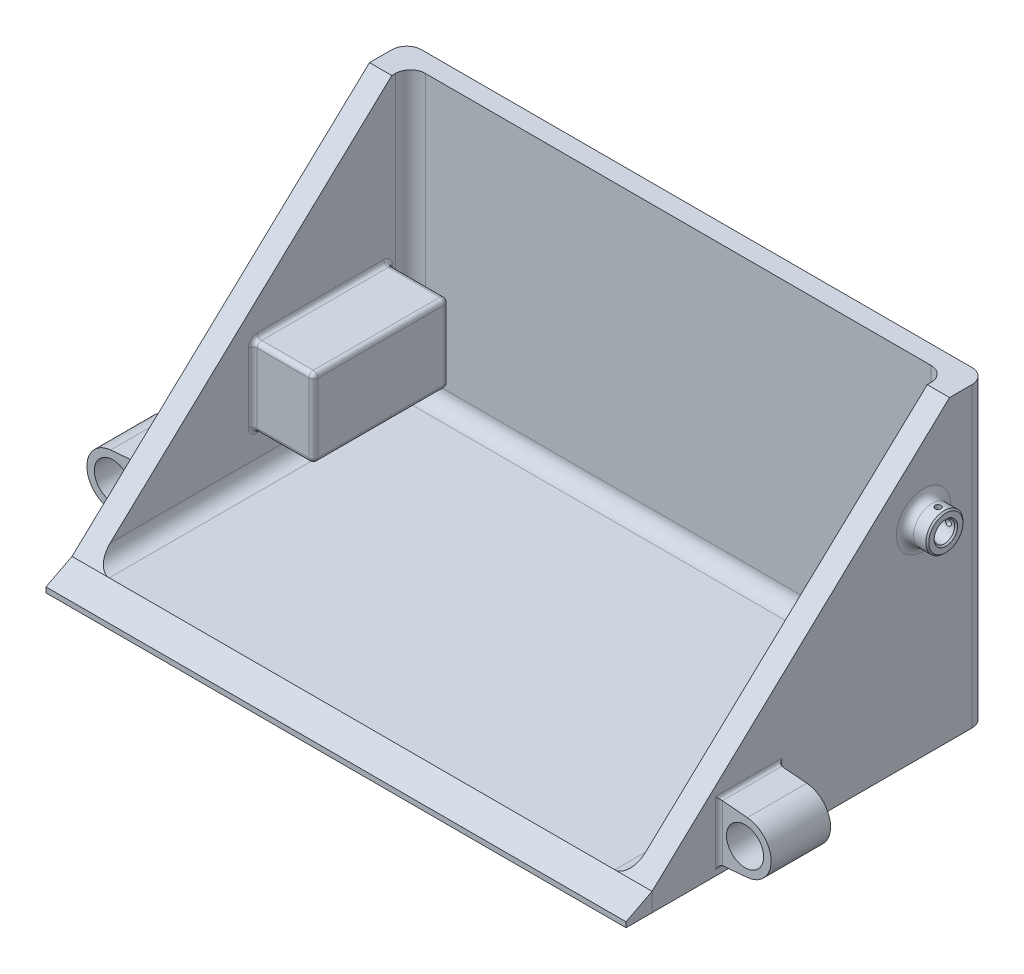
SolidWorks part; units mm, degrees
ref_plane "Front Plane" through (0, 0, 0) normal (0, 0, 1) x (1, 0, 0)
ref_plane "Top Plane" through (0, 0, 0) normal (0, 1, 0) x (1, 0, 0)
ref_plane "Right Plane" through (0, 0, 0) normal (1, 0, 0) x (0, 0, -1)
sketch "Sketch1" plane through (0, 0, 0) normal (0, 1, 0) x (1, 0, 0)
  line L1 (-99.06, 57.15) -> (99.06, 57.15)
  line L2 (-99.06, 57.15) -> (-99.06, -57.15)
  line L3 (-99.06, -57.15) -> (99.06, -57.15)
  line L4 (99.06, 57.15) -> (99.06, -57.15)
  line L5 (-99.06, 57.15) -> (99.06, -57.15) construction
  line L6 (-99.06, -57.15) -> (99.06, 57.15) construction
  point P0 (0, 0)
  dimension "D1" = 198.12
  dimension "D2" = 114.3
extrude "Boss-Extrude1" add sketch "Sketch1" along normal mid plane 6.35
sketch "Sketch3" plane through (-99.06, 0, 0) normal (-1, 0, 0) x (0, 0, 1)
  line L0 (-57.15, 3.175) -> (-57.15, 98.425)
  line L1 (-57.15, 98.425) -> (-44.45, 98.425)
  line L2 (-44.45, 98.425) -> (57.15, 3.175)
  line L3 (57.15, 3.175) -> (-57.15, 3.175)
  line L4 (-57.15, -3.175) -> (57.15, -3.175) construction
  dimension "D1" = 101.6
  dimension "D2" = 12.7
extrude "Boss-Extrude2" add sketch "Sketch3" against normal blind 7.62
mirror "Mirror1" about plane through (0, 0, 0) normal (1, 0, 0) of "Boss-Extrude2"
sketch "Sketch4" plane through (0, 3.175, 0) normal (0, 1, 0) x (1, 0, 0)
  line L0 (-91.44, 57.15) -> (91.44, 57.15)
  line L1 (91.44, 57.15) -> (91.44, 50.8)
  line L2 (91.44, 50.8) -> (-91.44, 50.8)
  line L3 (-91.44, 50.8) -> (-91.44, 57.15)
  dimension "D1" = 6.35
extrude "Boss-Extrude3" add sketch "Sketch4" along normal up to surface (95.25 mm away) up to face at (-95.25, 98.425, -50.8)
sketch "Sketch5" plane through (-99.06, 0, 0) normal (-1, 0, 0) x (0, 0, 1)
  line L1 (66.04, -3.175) -> (57.15, -3.175)
  line L2 (57.15, -3.175) -> (57.15, 3.175)
  line L3 (-57.15, 98.425) -> (-57.15, -3.175) construction
  line L4 (57.15, 3.175) -> (66.04, -1.397)
  line L5 (66.04, -1.397) -> (66.04, -3.175)
  dimension "D1" = 123.19
  dimension "D2" = 1.778
extrude "Boss-Extrude4" add sketch "Sketch5" along direction (1, 0, 0) on the side against the normal up to surface (198.12 mm away) separate body up to face at (99.06, 38.735, -8.89)
fillet "Fillet2" radius 5.08 5 edges at (91.44, 3.175, 3.175) (91.44, 50.8, -50.8) (0, 3.175, -50.8) (-91.44, 3.175, 3.175) (-91.44, 50.8, -50.8)
fillet "Fillet3" radius 5.08 2 edges at (99.06, 47.625, -57.15) (-99.06, 47.625, -57.15)
sketch "Sketch6" plane through (99.06, 0, 0) normal (1, 0, 0) x (0, 0, -1)
  line L0 (-57.15, -3.175) -> (52.07, -3.175) construction
  line L1 (57.15, 98.425) -> (57.15, -3.175) construction
  circle A0 centre (35.56, 66.675) radius 3.4925
  circle A1 centre (35.56, 66.675) radius 6.35
  dimension "D1" = 6.985
  dimension "D2" = 12.7
  dimension "D3" = 69.85
  dimension "D4" = 21.59
extrude "Boss-Extrude5" add sketch "Sketch6" along normal blind 7.62
mirror "Mirror2" about plane through (0, 0, 0) normal (1, 0, 0) of "Boss-Extrude5"
fillet "Fillet4" radius 2.921 2 edges at (99.06, 66.675, -29.21) (-99.06, 66.675, -41.91)
chamfer "Chamfer1" distance 0.508 angle 45 4 edges at (106.68, 66.675, -39.0525) (106.68, 66.675, -41.91) (-106.68, 66.675, -39.0525) (-106.68, 66.675, -41.91)
ref_plane "setscrew_lhs_plane" through (0, 73.025, 0) normal (0, 1, 0) x (1, 0, 0)
sketch "Sketch7" plane through (0, 73.025, 0) normal (0, 1, 0) x (1, 0, 0)
  line L0 (101.981, 29.21) -> (106.172, 29.21) construction
  line L1 (106.172, 41.91) -> (101.981, 41.91) construction
  line L2 (101.981, 29.21) -> (106.172, 29.21) construction
  line L3 (106.172, 41.91) -> (101.981, 41.91) construction
  line L4 (104.0765, 41.91) -> (104.0765, 29.21) construction
  circle A0 centre (104.0765, 35.56) radius 1.0033
  dimension "D1" = 2.0066
extrude "Cut-Extrude1" cut sketch "Sketch7" against normal blind 3.81
pattern_circular "CirPattern1" count 2 every 90 about axis through (106.68, 66.675, -35.56) along (-1, 0, 0) of "Cut-Extrude1"
mirror "Mirror3" about plane through (0, 0, 0) normal (1, 0, 0) of "CirPattern1"
sketch "Sketch8" plane through (-99.06, 0, 0) normal (-1, 0, 0) x (0, 0, 1)
  line L0 (-57.15, -3.175) -> (-57.15, 98.425) construction
  line L1 (-40.64, 41.275) -> (0.508, 41.275)
  line L2 (-40.64, 41.275) -> (-40.64, 19.685)
  line L3 (-40.64, 19.685) -> (0.508, 19.685)
  line L4 (0.508, 41.275) -> (0.508, 19.685)
  line L5 (-40.64, 41.275) -> (0.508, 19.685) construction
  line L6 (-40.64, 19.685) -> (0.508, 41.275) construction
  line L7 (-52.07, -3.175) -> (57.15, -3.175) construction
  point P0 (-20.066, 30.48)
  dimension "D1" = 16.51
  dimension "D2" = 41.148
  dimension "D3" = 22.86
  dimension "D4" = 21.59
extrude "Cut-Extrude2" cut sketch "Sketch8" against normal up to surface (7.62 mm away) up to face at (-91.44, 53.34, -21.0397)
sketch "Sketch9" plane through (-91.44, 0, 0) normal (1, 0, 0) x (0, 0, -1)
  line L0 (40.64, 41.275) -> (40.64, 19.685) construction
  line L1 (-0.508, 19.685) -> (-0.508, 41.275) construction
  line L2 (-0.508, 41.275) -> (40.64, 41.275) construction
  line L3 (40.64, 19.685) -> (-0.508, 19.685) construction
  line L4 (40.64, 41.275) -> (40.64, 19.685)
  line L5 (-0.508, 19.685) -> (-0.508, 41.275)
  line L6 (-0.508, 41.275) -> (40.64, 41.275)
  line L7 (40.64, 19.685) -> (-0.508, 19.685)
  line L8 (40.64, 30.48) -> (-0.508, 30.48) construction
  line L9 (20.066, 41.275) -> (20.066, 19.685) construction
  line L11 (-3.048, 17.145) -> (43.18, 17.145)
  line L12 (-3.048, 17.145) -> (-3.048, 43.815)
  line L13 (-3.048, 43.815) -> (43.18, 43.815)
  line L14 (43.18, 17.145) -> (43.18, 43.815)
  line L15 (-3.048, 17.145) -> (43.18, 43.815) construction
  line L16 (-3.048, 43.815) -> (43.18, 17.145) construction
  point P8 (20.066, 30.48)
  dimension "D1" = 2.54
  dimension "D2" = 2.54
extrude "Boss-Extrude6" add sketch "Sketch9" along normal blind 17.78
sketch "Sketch10" plane through (-73.66, 0, 0) normal (1, 0, 0) x (0, 0, -1)
  line L4 (43.18, 17.145) -> (43.18, 43.815)
  line L5 (43.18, 43.815) -> (-3.048, 43.815)
  line L6 (-3.048, 43.815) -> (-3.048, 17.145)
  line L7 (-3.048, 17.145) -> (43.18, 17.145)
  line L8 (43.18, 17.145) -> (43.18, 43.815)
  line L9 (43.18, 43.815) -> (-3.048, 43.815)
  line L10 (-3.048, 43.815) -> (-3.048, 17.145)
  line L11 (-3.048, 17.145) -> (43.18, 17.145)
  dimension "D1" = 0
extrude "Boss-Extrude7" add sketch "Sketch10" along normal blind 2.921
fillet "Fillet5" radius 1.524 12 edges at (-91.44, 30.48, 3.048) (-81.0895, 43.815, 3.048) (-91.44, 43.815, -20.066) (-70.739, 30.48, 3.048) (-70.739, 43.815, -20.066) (-70.739, 30.48, -43.18) (-81.0895, 43.815, -43.18) (-91.44, 30.48, -43.18) (-81.0895, 17.145, 3.048) (-70.739, 17.145, -20.066) (-81.0895, 17.145, -43.18) (-91.44, 17.145, -20.066)
fillet "Fillet6" radius 1.524 4 edges at (-86.36, 19.685, -40.64) (-86.36, 19.685, 0.508) (-86.36, 41.275, 0.508) (-86.36, 41.275, -40.64)
sketch "Sketch11" plane through (-99.06, 0, 0) normal (-1, 0, 0) x (0, 0, 1)
  line L0 (-20.066, 41.275) -> (-20.066, 19.685) construction
  line L1 (-39.116, 41.275) -> (-1.016, 41.275) construction
  line L2 (-1.016, 19.685) -> (-39.116, 19.685) construction
  line L3 (0.508, 30.48) -> (-40.64, 30.48) construction
  line L4 (0.508, 39.751) -> (0.508, 21.209) construction
  line L5 (-40.64, 21.209) -> (-40.64, 39.751) construction
  line L11 (-45.085, 35.56) -> (4.953, 35.56) construction
  line L12 (-40.64, 39.751) -> (-40.64, 21.209) construction
  line L13 (-40.64, 38.735) -> (-40.64, 22.225)
  line L14 (-40.64, 38.735) -> (-48.26, 38.735)
  line L15 (-48.26, 38.735) -> (-48.26, 22.225)
  line L16 (-48.26, 22.225) -> (-40.64, 22.225)
  line L17 (0.508, 38.735) -> (8.128, 38.735)
  line L18 (8.128, 38.735) -> (8.128, 22.225)
  line L19 (0.508, 38.735) -> (0.508, 22.225)
  line L20 (8.128, 22.225) -> (0.508, 22.225)
  circle A2 centre (-45.085, 35.56) radius 1.524
  circle A3 centre (4.953, 35.56) radius 1.524
  circle A4 centre (4.953, 25.4) radius 1.524
  circle A5 centre (-45.085, 25.4) radius 1.524
  point P16 (-20.066, 35.56)
  point P23 (-40.64, 30.48)
  dimension "D2" = 3.048
  dimension "D3" = 3.048
  dimension "D4" = 50.038
  dimension "D5" = 10.16
  dimension "D1" = 16.51
  dimension "D6" = 7.62
extrude "Boss-Extrude8" add sketch "Sketch11" along normal blind 3.81
ref_plane "Plane1" through (0, 0, -20.066) normal (0, 0, 1) x (1, 0, 0)
ref_plane "Plane2" through (0, 30.48, 0) normal (0, -1, 0) x (-1, 0, 0)
fillet "Fillet7" radius 1.27 6 edges at (-99.06, 22.225, 4.318) (-99.06, 30.48, 8.128) (-99.06, 38.735, 4.318) (-99.06, 22.225, -44.45) (-99.06, 30.48, -48.26) (-99.06, 38.735, -44.45)
ref_plane "Plane3" through (0, 0, 24.13) normal (0, 0, -1) x (-1, 0, 0)
ref_plane "Plane4" through (0, 0, -6.35) normal (0, 0, -1) x (-1, 0, 0)
sketch "Sketch12" plane through (0, 0, 24.13) normal (0, 0, -1) x (-1, 0, 0)
  line L0 (99.06, 98.425) -> (99.06, -3.175) construction
  line L1 (-93.98, -3.175) -> (93.98, -3.175) construction
  line L2 (108.7248, 18.3812) -> (99.06, 19.2267)
  line L3 (108.7248, 0.6688) -> (99.06, -0.1767)
  line L4 (107.95, 9.525) -> (99.06, 9.525) construction
  line L5 (99.06, 19.2267) -> (99.06, -0.1767)
  circle A0 centre (107.95, 9.525) radius 6.35
  arc A1 (108.7248, 0.6688) -> (108.7248, 18.3812) centre (107.95, 9.525) ccw
  dimension "D1" = 12.7
  dimension "D2" = 17.78
  dimension "D5" = 5
  dimension "D3" = 8.89
  dimension "D4" = 12.7
  dimension "D6" = 5
extrude "Boss-Extrude9" add sketch "Sketch12" along normal mid plane 20.32
mirror "Mirror4" about plane through (0, 0, 0) normal (1, 0, 0) of "Boss-Extrude9"
fillet "Fillet8" radius 1.27 8 edges at (-99.06, -0.1767, 24.13) (-99.06, 9.525, 13.97) (-99.06, 9.525, 34.29) (-99.06, 19.2267, 24.13) (99.06, 19.2267, 24.13) (99.06, 9.525, 13.97) (99.06, -0.1767, 24.13) (99.06, 9.525, 34.29)
equation "\"D3@Sketch11\"=\"D2@Sketch11\""
